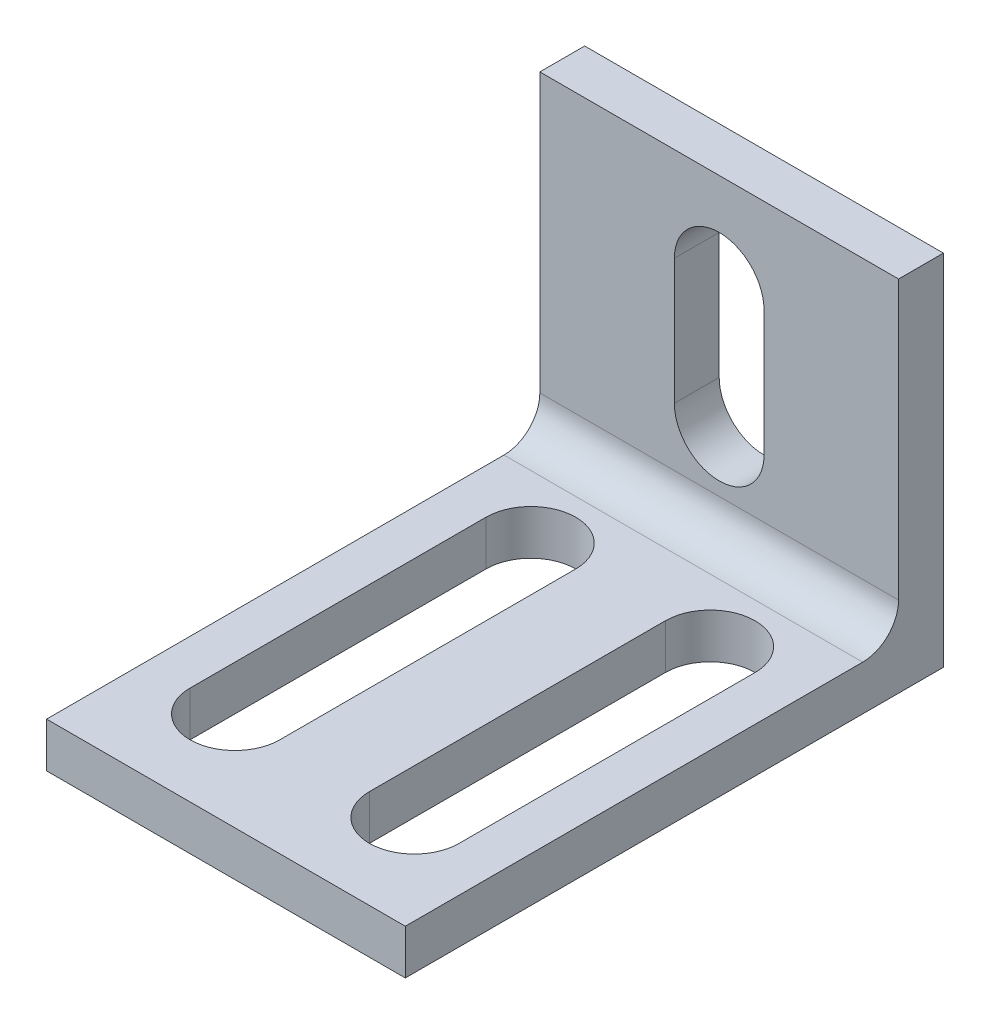
SolidWorks part; units mm, degrees
ref_plane "Front Plane" through (0, 0, 0) normal (0, 0, 1) x (1, 0, 0)
ref_plane "Top Plane" through (0, 0, 0) normal (0, 1, 0) x (1, 0, 0)
ref_plane "Right Plane" through (0, 0, 0) normal (1, 0, 0) x (0, 0, -1)
sketch "Sketch1" plane through (0, 0, 0) normal (1, 0, 0) x (0, 0, -1)
  line L0 (19.05, 12.7) -> (19.05, -12.7) construction
  line L1 (19.05, -12.7) -> (-19.05, -12.7) construction
  line L2 (15.875, 12.7) -> (15.875, -9.525) construction
  line L3 (15.875, -9.525) -> (-19.05, -9.525) construction
  point P2 (0, -12.7)
  point P4 (19.05, 0)
  dimension "Height" = 25.4
  dimension "Length" = 38.1
  dimension "Thickness" = 3.175
sketch "Sketch3" plane through (0, 0, 0) normal (0, 0, 1) x (1, 0, 0)
  line L0 (-12.7, -9.525) -> (12.7, -9.525) construction
  line L2 (0, 12.7) -> (0, -12.7) construction
  line L3 (0, 12.7) -> (0, -9.525) construction
  line L4 (0, 6.0325) -> (0, -2.8575) construction
  line L5 (3.175, 6.0325) -> (3.175, -2.8575) construction
  line L6 (-3.175, 6.0325) -> (-3.175, -2.8575) construction
  arc A0 (3.175, 6.0325) -> (-3.175, 6.0325) centre (0, 6.0325) ccw construction
  arc A1 (-3.175, -2.8575) -> (3.175, -2.8575) centre (0, -2.8575) ccw construction
  point P3 (0, -9.525)
  point P9 (0, 1.5875)
  dimension "Width" = 25.4
  dimension "D1" = 22.225
  dimension "D2" = 8.89
  dimension "Screw Size" = 6.35
sketch "Sketch2" plane through (0, 0, 0) normal (1, 0, 0) x (0, 0, -1)
  line L0 (15.875, -9.525) -> (-19.05, -9.525) construction
  line L1 (19.05, -12.7) -> (-19.05, -12.7) construction
  line L2 (19.05, 12.7) -> (19.05, -12.7) construction
  line L3 (15.875, 12.7) -> (15.875, -9.525) construction
  line L4 (15.875, -9.525) -> (-19.05, -9.525)
  line L5 (19.05, -12.7) -> (-19.05, -12.7)
  line L6 (19.05, 12.7) -> (19.05, -12.7)
  line L7 (15.875, 12.7) -> (15.875, -9.525)
  line L8 (-19.05, -9.525) -> (-19.05, -12.7)
  line L9 (15.875, 12.7) -> (19.05, 12.7)
extrude "Boss-Extrude1" add sketch "Sketch2" along normal up to vertex (12.7 mm away) and the other way up to vertex (12.7 mm away) up to point (12.7, -9.525, 0) other way up to point (-12.7, -9.525, 0)
sketch "Sketch4" plane through (0, 0, -15.875) normal (0, 0, 1) x (1, 0, 0)
  line L0 (-3.175, 6.0325) -> (-3.175, -2.8575) construction
  line L1 (-3.175, 6.0325) -> (-3.175, -2.8575)
  line L2 (3.175, 6.0325) -> (3.175, -2.8575) construction
  line L3 (3.175, 6.0325) -> (3.175, -2.8575)
  arc A0 (-3.175, -2.8575) -> (3.175, -2.8575) centre (0, -2.8575) ccw construction
  arc A1 (3.175, 6.0325) -> (-3.175, 6.0325) centre (0, 6.0325) ccw construction
  arc A2 (-3.175, -2.8575) -> (3.175, -2.8575) centre (0, -2.8575) ccw
  arc A3 (3.175, 6.0325) -> (-3.175, 6.0325) centre (0, 6.0325) ccw
  point P7 (3.175, 6.0325)
extrude "Cut-Extrude1" cut sketch "Sketch4" against normal through all
sketch "Sketch5" plane through (0, -9.525, 0) normal (0, 1, 0) x (1, 0, 0)
  line L0 (-6.35, 8.89) -> (-6.35, -12.065) construction
  line L1 (-3.175, 8.89) -> (-3.175, -12.065)
  line L2 (-9.525, 8.89) -> (-9.525, -12.065)
  line L3 (0, 15.875) -> (0, -19.05) construction
  line L4 (12.7, 15.875) -> (-12.7, 15.875) construction
  line L5 (0, 19.05) -> (0, -19.05) construction
  line L6 (0, 15.875) -> (0, -19.05) construction
  line L7 (6.35, 8.89) -> (6.35, -12.065) construction
  line L8 (3.175, 8.89) -> (3.175, -12.065)
  line L9 (9.525, 8.89) -> (9.525, -12.065)
  arc A0 (-3.175, 8.89) -> (-9.525, 8.89) centre (-6.35, 8.89) ccw
  arc A1 (-9.525, -12.065) -> (-3.175, -12.065) centre (-6.35, -12.065) ccw
  arc A2 (3.175, 8.89) -> (9.525, 8.89) centre (6.35, 8.89) cw
  arc A3 (9.525, -12.065) -> (3.175, -12.065) centre (6.35, -12.065) cw
  point P2 (-6.35, -1.5875)
  point P15 (9.525, -1.5875)
  point P19 (0, -1.5875)
  point P23 (6.35, -1.5875)
  dimension "Thread Diameter" = 6.35
  dimension "D2" = 34.925
  dimension "D3" = 20.955
  dimension "D4" = 12.7
extrude "Cut-Extrude2" cut sketch "Sketch5" against normal blind 38.1
fillet "Fillet1" radius 2.54 1 edges at (0, -9.525, -15.875)
ref_plane "Contact Plane 1" through (0, -9.525, 0) normal (0, 1, 0) x (1, 0, 0)
ref_axis "Center Axis 1" through (0, -2.8575, -19.05) along (0, 0, 1)
ref_axis "Center Axis 2" through (0, 6.0325, -19.05) along (0, 0, 1)
ref_axis "Center Axis 3" through (-6.35, -12.7, -8.89) along (0, 1, 0)
ref_axis "Center Axis 4" through (6.35, -12.7, -8.89) along (0, 1, 0)
equation "\"D2@Sketch3\"=\"D1@Sketch3\"*0.4"
equation "\"D3@Sketch5\"=\"D2@Sketch5\"*0.6"
equation "\"D4@Sketch5\"=\"Width@Sketch3\"*0.5"
